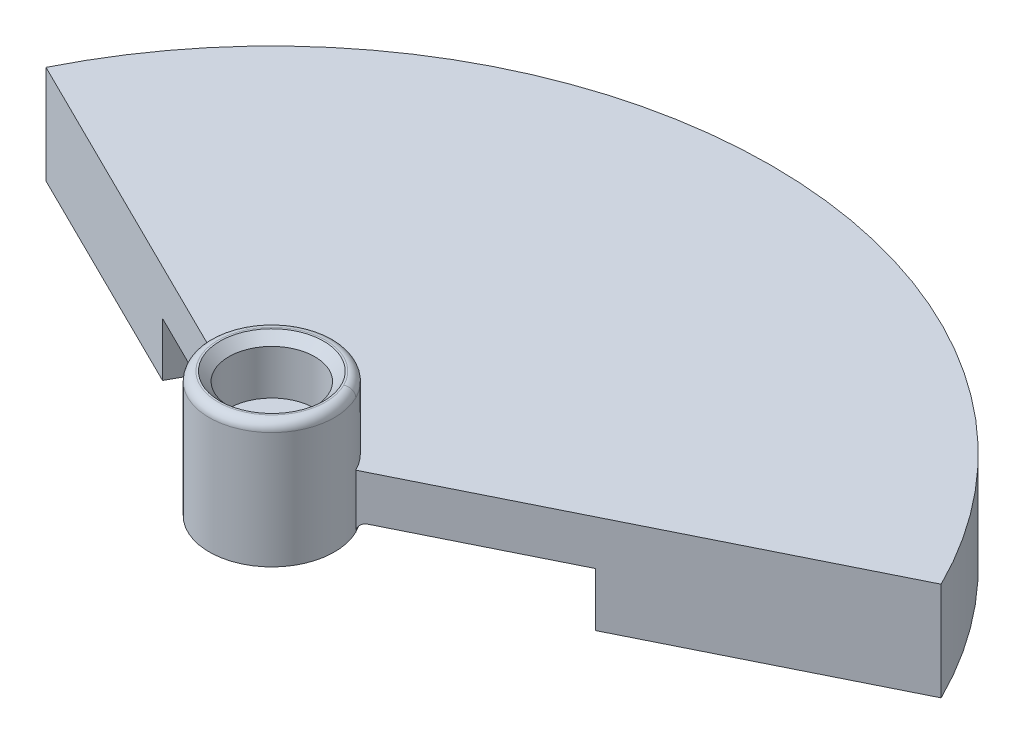
SolidWorks part; units mm, degrees
ref_plane "Front Plane" through (0, 0, 0) normal (0, 0, 1) x (1, 0, 0)
ref_plane "Top Plane" through (0, 0, 0) normal (0, 1, 0) x (1, 0, 0)
ref_plane "Right Plane" through (0, 0, 0) normal (1, 0, 0) x (0, 0, -1)
sketch "Sketch1" plane through (0, 0, 0) normal (0, 1, 0) x (1, 0, 0)
  circle A0 centre (0, 0) radius 2.5
  circle A1 centre (0, 0) radius 3.5
  dimension "D1" = 5
  dimension "D2" = 1
extrude "Boss-Extrude1" add sketch "Sketch1" along normal blind 3
sketch "Sketch2" plane through (0, 3, 0) normal (0, 1, 0) x (1, 0, 0)
  circle A0 centre (0, 0) radius 3.5
extrude "Boss-Extrude2" add sketch "Sketch2" along normal blind 1
sketch "Sketch3" plane through (0, 4, 0) normal (0, 1, 0) x (1, 0, 0)
  circle A0 centre (0, 0) radius 1.3
  dimension "D1" = 2.6
extrude "Cut-Extrude1" cut sketch "Sketch3" against normal up to next
sketch "Sketch4" plane through (0, 4, 0) normal (0, 1, 0) x (1, 0, 0)
  circle A0 centre (0, 0) radius 2.4
  circle A1 centre (0, 0) radius 3.5
  dimension "D1" = 4.8
extrude "Boss-Extrude3" add sketch "Sketch4" along normal blind 3
chamfer "Chamfer1" distance 0.5 angle 45 2 edges at (0, 7, 2.4) (0, 0, 2.5)
ref_plane "Plane1" through (0, 3.5, 0) normal (0, 1, 0) x (1, 0, 0)
sketch "Sketch5" plane through (0, 3.5, 0) normal (0, 1, 0) x (1, 0, 0)
  line L0 (0, 0) -> (15.4603, 0) construction
  arc A0 (-0.0885, -3.4989) -> (21.9115, -1) centre (1.9409, 76.7271) ccw
  circle A1 centre (0, 0) radius 3.5 construction
  arc A3 (-0.0885, 3.4989) -> (21.9115, 1) centre (1.9409, -76.7271) cw
  arc A4 (21.9115, 1) -> (21.9115, -1) centre (21.6546, 0) cw
  arc A5 (-0.0885, -3.4989) -> (-0.0885, 3.4989) centre (0, 0) ccw
  dimension "D1" = 22
  dimension "D2" = 1
extrude "Boss-Extrude4" [suppressed] add sketch "Sketch5" along normal blind 1 and the other way blind 1
sketch "Sketch6" plane through (0, 3.5, 0) normal (0, 1, 0) x (1, 0, 0)
  line L0 (-25, 12.3859) -> (-3.1362, 1.5538)
  line L1 (25, 12.3859) -> (3.1362, 1.5538)
  line L2 (0, 0) -> (0, -4.7859) construction
  arc A0 (-25, 12.3859) -> (25, 12.3859) centre (0, 0) cw
  circle A1 centre (0, 0) radius 2.9 construction
  circle A2 centre (0, 0) radius 3.5 construction
  arc A3 (-3.1362, 1.5538) -> (3.1362, 1.5538) centre (0, 0) cw
  dimension "D1" = 25
extrude "Boss-Extrude5" add sketch "Sketch6" along normal up to surface (3.5 mm away) and the other way offset from surface 0.5 up to face at (0, 7, 2.9) other way up to face at (0, 0, 3)
fillet "Fillet1" radius 0.5 2 edges at (0, 7, 3.5) (0, 0.5, -3.5)
sketch "Sketch7" plane through (0, 0.5, 0) normal (0, -1, 0) x (1, 0, 0)
  line L0 (-3.5842, -1.7758) -> (-25, -12.3859) construction
  line L1 (25, -12.3859) -> (3.5842, -1.7758) construction
  line L4 (25, -12.3859) -> (3.5842, -1.7758)
  line L5 (-3.5842, -1.7758) -> (-25, -12.3859)
  line L6 (25, -12.3859) -> (12.0968, -5.9932)
  line L7 (-12.0968, -5.9932) -> (-25, -12.3859)
  arc A0 (-12.0968, -5.9932) -> (12.0968, -5.9932) centre (0, 0) ccw
  arc A2 (-3.1362, -1.5538) -> (3.1362, -1.5538) centre (0, 0) ccw construction
  arc A6 (-3.5842, -1.7758) -> (3.5842, -1.7758) centre (0, 0) ccw
  arc A7 (-25, -12.3859) -> (25, -12.3859) centre (0, 0) ccw
  arc A9 (-25, -12.3859) -> (25, -12.3859) centre (0, 0) ccw
  point P10 (0, -13.5)
  dimension "D1" = 10
  dimension "D2" = 0
extrude "Boss-Extrude6" add sketch "Sketch7" along normal blind 3
sketch "Sketch8" plane through (0, 7, 0) normal (0, 1, 0) x (1, 0, 0)
  line L2 (2.6882, 1.3318) -> (25, 12.3859)
  line L3 (-25, 12.3859) -> (-2.6882, 1.3318)
  line L4 (3.1362, 1.5538) -> (25, 12.3859)
  line L5 (-25, 12.3859) -> (-3.1362, 1.5538)
  arc A1 (-3.1362, 1.5538) -> (3.1362, 1.5538) centre (0, 0) cw
  arc A2 (-2.6882, 1.3318) -> (2.6882, 1.3318) centre (0, 0) ccw
  arc A3 (25, 12.3859) -> (-25, 12.3859) centre (0, 0) ccw
  arc A5 (25, 12.3859) -> (-25, 12.3859) centre (0, 0) ccw
  arc A6 (-3.1362, 1.5538) -> (3.1362, 1.5538) centre (0, 0) ccw construction
  dimension "D1" = 0
extrude "Cut-Extrude2" cut sketch "Sketch8" against normal blind 4
fillet "Fillet3" radius 0.5 1 edges at (0, 7, -3.5)
